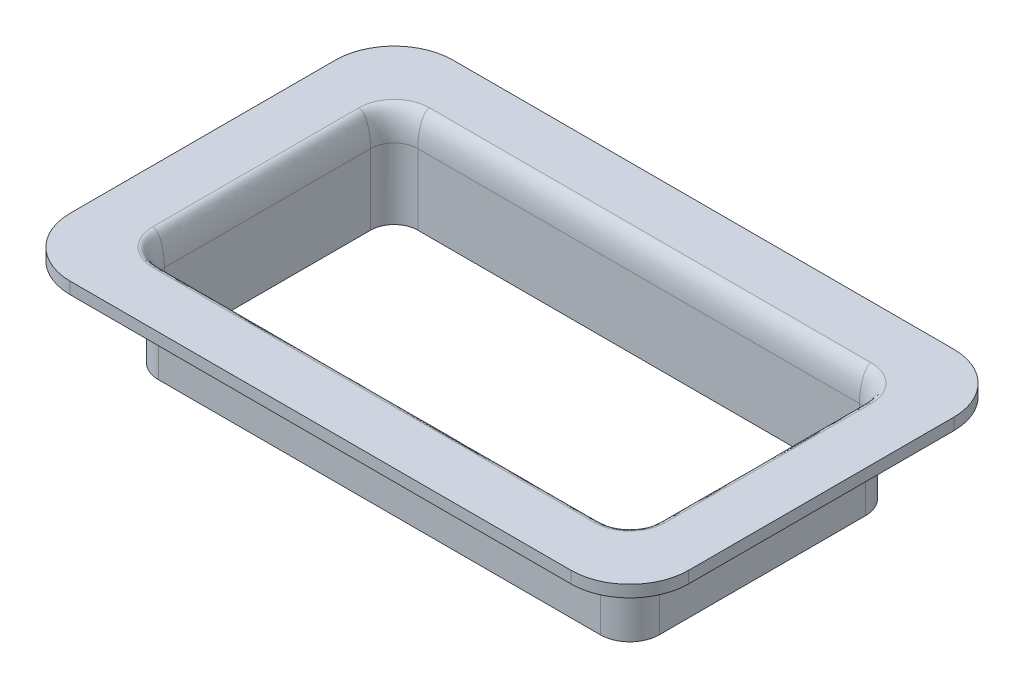
SolidWorks part; units mm, degrees
ref_plane "Front Plane" through (0, 0, 0) normal (0, 0, 1) x (1, 0, 0)
ref_plane "Top Plane" through (0, 0, 0) normal (0, 1, 0) x (1, 0, 0)
ref_plane "Right Plane" through (0, 0, 0) normal (1, 0, 0) x (0, 0, -1)
sketch "Sketch1" plane through (0, 0, 0) normal (0, 1, 0) x (1, 0, 0)
  line L0 (-52.705, 22.225) -> (-52.705, -22.225)
  line L1 (-47.625, 28.575) -> (47.625, 28.575)
  line L2 (-53.975, 22.225) -> (-53.975, -22.225)
  line L3 (-47.625, -28.575) -> (47.625, -28.575)
  line L4 (53.975, 22.225) -> (53.975, -22.225)
  line L5 (-53.975, 28.575) -> (53.975, -28.575) construction
  line L6 (-53.975, -28.575) -> (53.975, 28.575) construction
  line L7 (-47.625, -27.305) -> (47.625, -27.305)
  line L8 (52.705, 22.225) -> (52.705, -22.225)
  line L9 (-47.625, 27.305) -> (47.625, 27.305)
  arc A0 (47.625, 28.575) -> (53.975, 22.225) centre (47.625, 22.225) cw
  arc A1 (47.625, -28.575) -> (53.975, -22.225) centre (47.625, -22.225) ccw
  arc A2 (-53.975, -22.225) -> (-47.625, -28.575) centre (-47.625, -22.225) ccw
  arc A3 (-47.625, 28.575) -> (-53.975, 22.225) centre (-47.625, 22.225) ccw
  arc A4 (-52.705, -22.225) -> (-47.625, -27.305) centre (-47.625, -22.225) ccw
  arc A5 (47.625, -27.305) -> (52.705, -22.225) centre (47.625, -22.225) ccw
  arc A6 (47.625, 27.305) -> (52.705, 22.225) centre (47.625, 22.225) cw
  arc A7 (-47.625, 27.305) -> (-52.705, 22.225) centre (-47.625, 22.225) ccw
  point P0 (0, 0)
  dimension "D1" = 6.35
  dimension "D2" = 107.95
  dimension "D3" = 57.15
  dimension "D4" = 1.27
extrude "Boss-Extrude1" add sketch "Sketch1" along normal blind 19.05
sketch "Sketch2" plane through (0, 19.05, 0) normal (0, 1, 0) x (1, 0, 0)
  line L0 (47.625, 28.575) -> (-47.625, 28.575) construction
  line L1 (-53.975, -41.275) -> (53.975, -41.275)
  line L2 (-66.675, -28.575) -> (-66.675, 28.575)
  line L3 (-53.975, 41.275) -> (53.975, 41.275)
  line L4 (66.675, -28.575) -> (66.675, 28.575)
  line L5 (-66.675, -41.275) -> (66.675, 41.275) construction
  line L6 (-66.675, 41.275) -> (66.675, -41.275) construction
  line L7 (-53.975, 22.225) -> (-53.975, -22.225) construction
  line L16 (52.705, -22.225) -> (52.705, 22.225)
  line L17 (-47.625, -27.305) -> (47.625, -27.305)
  line L18 (-52.705, 22.225) -> (-52.705, -22.225)
  line L19 (47.625, 27.305) -> (-47.625, 27.305)
  line L20 (52.705, -22.225) -> (52.705, 22.225)
  line L21 (-47.625, -27.305) -> (47.625, -27.305)
  line L22 (-52.705, 22.225) -> (-52.705, -22.225)
  line L23 (47.625, 27.305) -> (-47.625, 27.305)
  arc A0 (53.975, 41.275) -> (66.675, 28.575) centre (53.975, 28.575) cw
  arc A1 (53.975, -41.275) -> (66.675, -28.575) centre (53.975, -28.575) ccw
  arc A2 (-53.975, -41.275) -> (-66.675, -28.575) centre (-53.975, -28.575) cw
  arc A3 (-66.675, 28.575) -> (-53.975, 41.275) centre (-53.975, 28.575) cw
  arc A12 (52.705, 22.225) -> (47.625, 27.305) centre (47.625, 22.225) ccw
  arc A13 (47.625, -27.305) -> (52.705, -22.225) centre (47.625, -22.225) ccw
  arc A14 (-52.705, -22.225) -> (-47.625, -27.305) centre (-47.625, -22.225) ccw
  arc A15 (-47.625, 27.305) -> (-52.705, 22.225) centre (-47.625, 22.225) ccw
  arc A16 (52.705, 22.225) -> (47.625, 27.305) centre (47.625, 22.225) ccw
  arc A17 (47.625, -27.305) -> (52.705, -22.225) centre (47.625, -22.225) ccw
  arc A18 (-52.705, -22.225) -> (-47.625, -27.305) centre (-47.625, -22.225) ccw
  arc A19 (-47.625, 27.305) -> (-52.705, 22.225) centre (-47.625, 22.225) ccw
  point P0 (0, 0)
  dimension "D3" = 12.7
  dimension "D1" = 12.7
  dimension "D2" = 12.7
  dimension "D4" = 1.27
extrude "Boss-Extrude2" add sketch "Sketch2" along normal blind 2.54
fillet "Fillet1" radius 6.35 8 edges at (-52.1151, 19.05, -26.7151) (0, 19.05, -28.575) (52.1151, 19.05, -26.7151) (53.975, 19.05, 0) (52.1151, 19.05, 26.7151) (0, 19.05, 28.575) (-52.1151, 19.05, 26.7151) (-53.975, 19.05, 0)
fillet "Fillet3" radius 2.54 8 edges at (51.2171, 21.59, -25.8171) (52.705, 21.59, 0) (51.2171, 21.59, 25.8171) (0, 21.59, 27.305) (-51.2171, 21.59, 25.8171) (-52.705, 21.59, 0) (-51.2171, 21.59, -25.8171) (0, 21.59, -27.305) second distance 6.35 first distance on face at (0, 21.59, 0)
